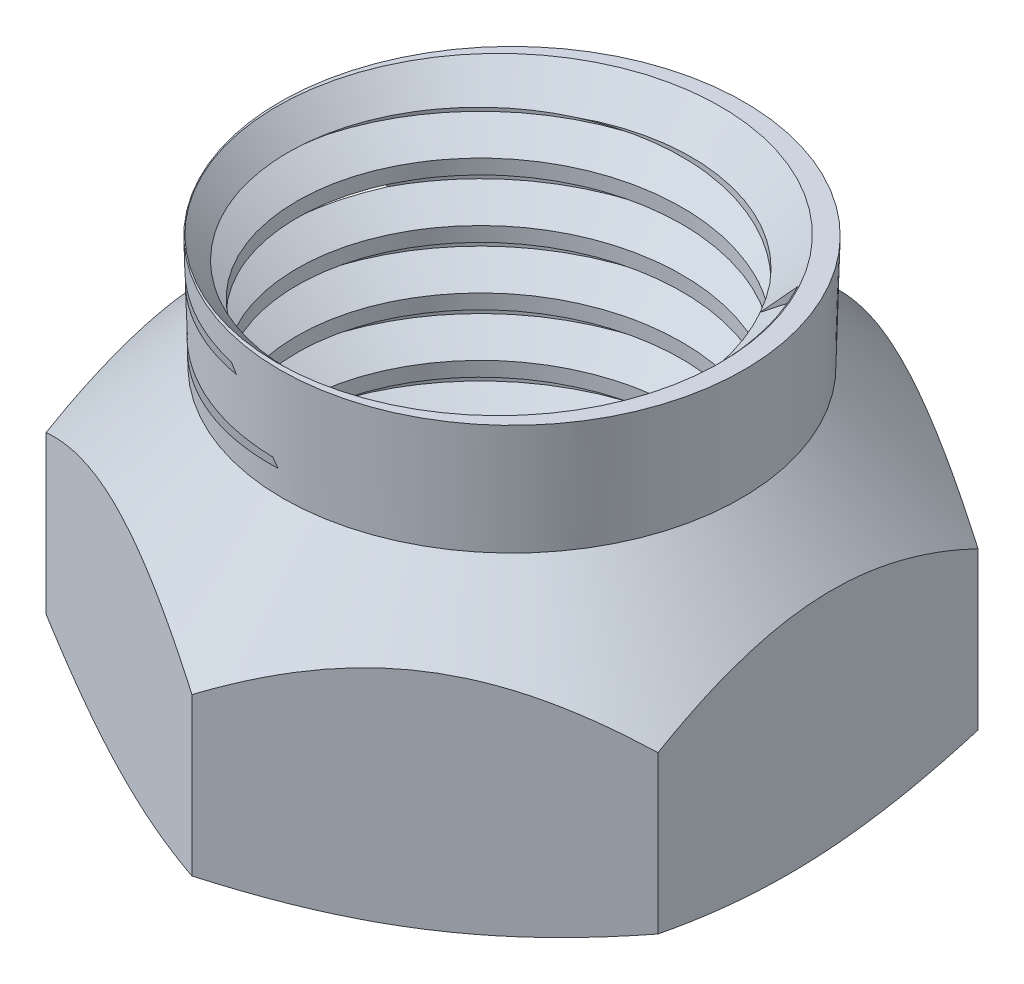
SolidWorks part; units mm, degrees
ref_plane "Front Plane" through (0, 0, 0) normal (0, 0, 1) x (1, 0, 0)
ref_plane "Top Plane" through (0, 0, 0) normal (0, 1, 0) x (1, 0, 0)
ref_plane "Right Plane" through (0, 0, 0) normal (1, 0, 0) x (0, 0, -1)
sketch "Sketch2" plane through (0, 0, 0) normal (0, 1, 0) x (1, 0, 0)
  line L1 (-0.285, 5.7665) -> (-5.1364, 2.6364)
  line L2 (-5.1364, 2.6364) -> (-4.8514, -3.1301)
  line L3 (-4.8514, -3.1301) -> (0.285, -5.7665)
  line L4 (0.285, -5.7665) -> (5.1364, -2.6364)
  line L5 (5.1364, -2.6364) -> (4.8514, 3.1301)
  line L6 (4.8514, 3.1301) -> (-0.285, 5.7665)
  circle A1 centre (0, 0) radius 5 construction
  dimension "D2" = 10
extrude "Boss-Extrude1" add sketch "Sketch2" along normal blind 4.9
sketch "Sketch3" plane through (0, 0, 0) normal (0, -1, 0) x (1, 0, 0)
  circle A0 centre (0, 0) radius 5
extrude "Cut-Extrude1" cut sketch "Sketch3" against normal blind 4.9 draft 65 flip side to cut
sketch "Sketch4" plane through (0, 4.9, 0) normal (0, 1, 0) x (1, 0, 0)
  circle A0 centre (0, 0) radius 3.925
  dimension "D1" = 7.85
extrude "Cut-Extrude3" cut sketch "Sketch4" against normal blind 4.9 draft 45 flip side to cut
sketch "Sketch16" plane through (0, 0, 0) normal (0, 0, 1) x (1, 0, 0)
  line L0 (0, 4.9) -> (0, 6.83)
  line L1 (3.925, 4.9) -> (-3.925, 4.9) construction
  line L2 (0, 6.83) -> (-3.975, 6.83)
  line L3 (-3.925, 4.9) -> (0, 4.9)
  line L4 (-3.975, 6.83) -> (-3.925, 4.9)
  line L5 (0, 6.83) -> (0, -1.7027) construction
revolve "Revolve1" add sketch "Sketch16" angle 360 about L5
hole_wizard "M6 Clearance Hole1" positions "Sketch13" profile "Sketch12" hole size "M6" standard "ANSI Metric"
sketch "Sketch13" plane through (0, 0, 0) normal (0, -1, 0) x (-1, 0, 0)
  point P0 (0.1349, -0.0944)
sketch "Sketch12" plane through (-0.1349, 0, 0.0944) normal (1, 0, 0) x (0, 0, -1)
  line L0 (0, 0) -> (0, 12.08)
  line L1 (0, 12.08) -> (3.3, 10.0972)
  line L2 (3.3, 10.0972) -> (3.3, 0)
  line L5 (3.3, 0) -> (0, 0)
  line L10 (0, 12.08) -> (-3.3, 10.0972) construction
  line L11 (0, -6.35) -> (0, 107.95) construction
  dimension "Hole Dia." = 6.6
  dimension "Hole Depth" = 12.08
  dimension "Drill Angle" = 118
chamfer "Chamfer3" distance 0.25 angle 45 1 edges at (-0.1349, 0, -3.2056)
chamfer "Chamfer4" distance 0.5 angle 45 1 edges at (-0.1349, 6.83, 3.3944)
thread "Thread2" pitch 1 method cut profile "Thread Profile2" start angle 0, offset 0, length 0, pitch 1, diameter 6.6
ref_plane "Plane2" through (3.1651, 0.25, 0.0944) normal (0, 0, 1) x (1, 0, 0)
sketch "Thread Profile2" plane through (3.1651, 0.25, 0.0944) normal (0, 0, 1) x (1, 0, 0)
  line L0 (0, 0) -> (0, 1) construction
  line L1 (0, 0) -> (0.5413, 0.3125)
  line L2 (0.5413, 0.3125) -> (0.5413, 0.4375)
  line L3 (0.5413, 0.4375) -> (0, 0.75)
  line L4 (0.5413, 0.375) -> (0, 0.375) construction
  line L11 (0, 0) -> (0, 0.75)
  point P2 (0, 0)
  dimension "Pitch" = 1
  dimension "Profile_Angle" = 60
  dimension "Profile_Land" = 0.125
  dimension "Profile_Height" = 0.5413
